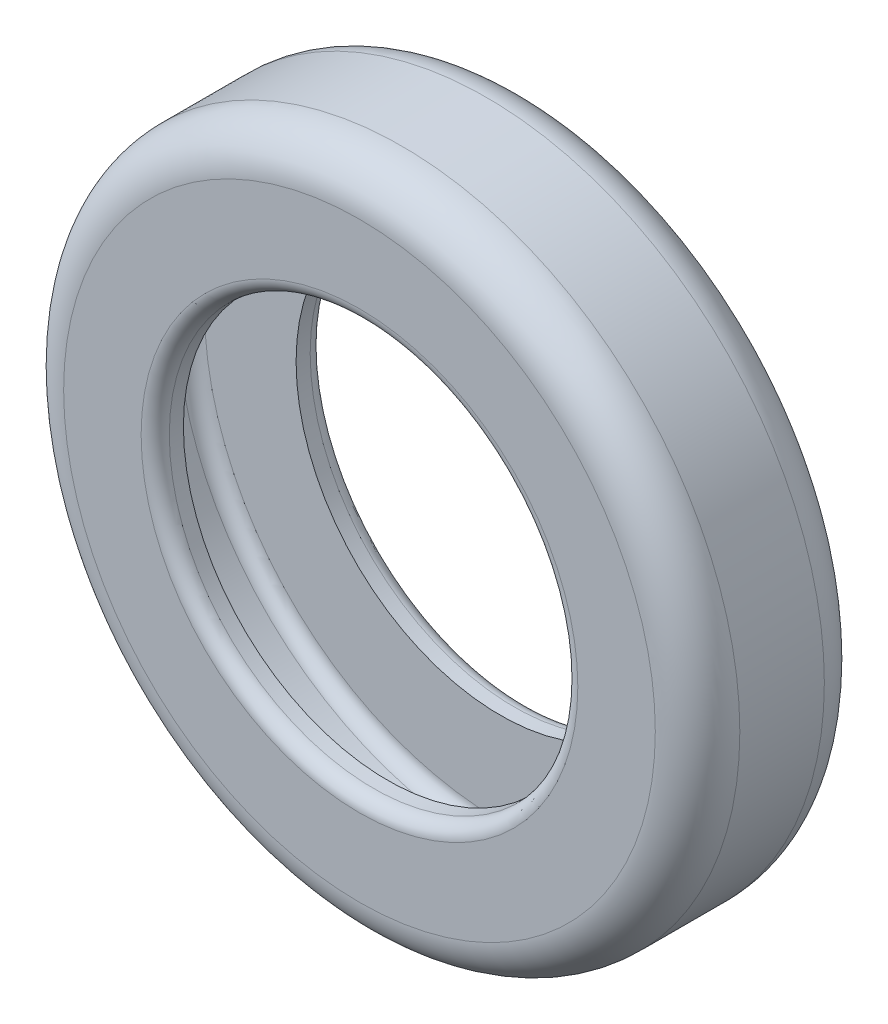
SolidWorks part; units mm, degrees
other "Markup1"
sketch "Sketch3" plane through (-314.2, -314.2, 0) normal (0, 0, 1) x (1, 0, 0)
other "Markup2"
sketch "Sketch4" plane through (-314.2, -314.2, 0) normal (0, 0, 1) x (1, 0, 0)
ref_plane "Front Plane" through (0, 0, 0) normal (0, 0, 1) x (1, 0, 0)
ref_plane "Top Plane" through (0, 0, 0) normal (0, 1, 0) x (1, 0, 0)
ref_plane "Right Plane" through (0, 0, 0) normal (1, 0, 0) x (0, 0, -1)
sketch "Sketch1" plane through (0, 0, 0) normal (0, 0, 1) x (1, 0, 0)
  circle A0 centre (0, 0) radius 145
  dimension "D1" = 290
extrude "Extrude-Thin1" add sketch "Sketch1" against normal blind 120 thin thin type one direction wall 95
fillet "Fillet1" radius 30 2 edges at (240, 0, -120) (240, 0, 0)
fillet "Fillet2" radius 10 1 edges at (145, 0, 0)
fillet "Fillet3" radius 10 1 edges at (145, 0, -120)
shell "Shell1" thickness 20 removed face at (145, 0, -110)
